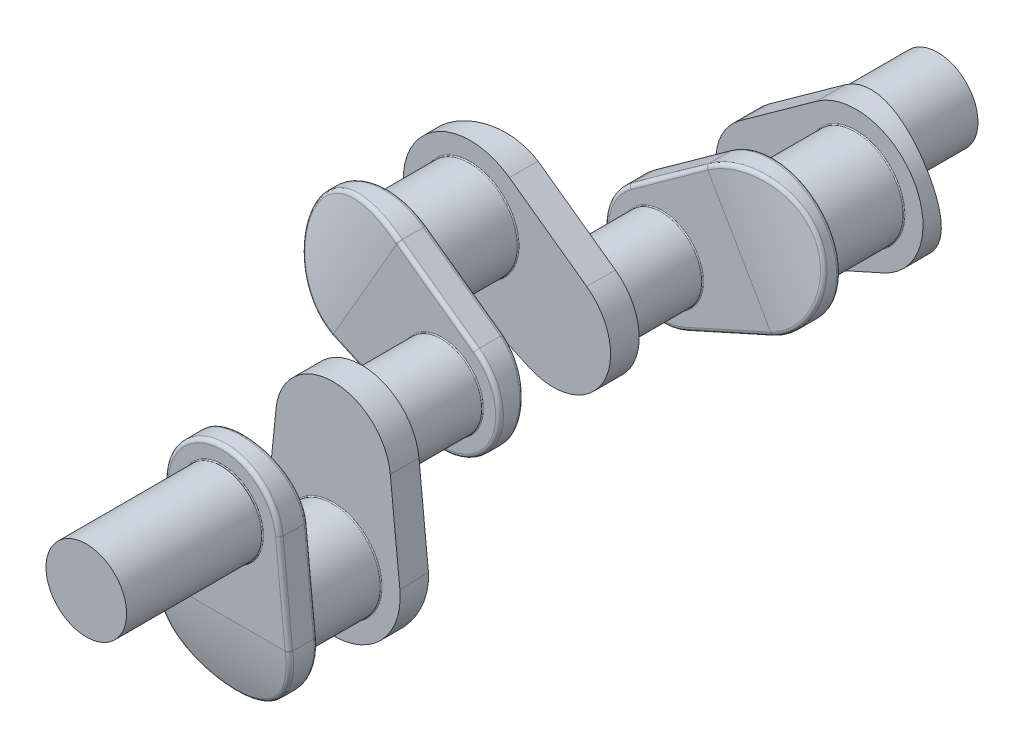
SolidWorks part; units mm, degrees
ref_plane "Front Plane" through (0, 0, 0) normal (0, 0, 1) x (1, 0, 0)
ref_plane "Top Plane" through (0, 0, 0) normal (0, 1, 0) x (1, 0, 0)
ref_plane "Right Plane" through (0, 0, 0) normal (1, 0, 0) x (0, 0, -1)
sketch "Sketch1" plane through (0, 0, 0) normal (0, 0, 1) x (1, 0, 0)
  circle A0 centre (0, 0) radius 31.75
  dimension "D1" = 63.5
extrude "Boss-Extrude1" add sketch "Sketch1" along normal blind 27.31
sketch "Sketch2" plane through (0, 0, 27.31) normal (0, 0, 1) x (1, 0, 0)
  line L0 (-37.909, 67.31) -> (-44.2272, 4.445)
  line L1 (37.909, 67.31) -> (44.2272, 4.445)
  arc A0 (-44.2272, 4.445) -> (44.2272, 4.445) centre (0, 0) ccw
  circle A2 centre (0, 0) radius 31.75 construction
  arc A3 (37.909, 67.31) -> (-37.909, 67.31) centre (0, 63.5) ccw
  dimension "D1" = 12.7
  dimension "D2" = 63.5
extrude "Boss-Extrude2" add sketch "Sketch2" along normal blind 19
sketch "Sketch3" plane through (0, 0, 46.31) normal (0, 0, 1) x (1, 0, 0)
  circle A0 centre (0, 63.5) radius 26.75
  point P3 (0, 0)
  point P4 (0, 0)
  dimension "D1" = 53.5
extrude "Boss-Extrude3" add sketch "Sketch3" along normal blind 26.67 contours A0
sketch "Sketch4" plane through (0, 0, 0) normal (1, 0, 0) x (0, 0, -1)
  line L0 (-46.31, -44.45) -> (-27.31, -44.45) construction
  line L1 (-46.31, 4.445) -> (-69.1204, 4.445)
  line L2 (-69.1204, 4.445) -> (-69.1204, -44.45)
  line L3 (-69.1204, -44.45) -> (-36.81, -44.45)
  arc A0 (-46.31, 4.445) -> (-36.81, -44.45) centre (122.5264, 11.8785) ccw
  dimension "D1" = 169
extrude "Cut-Extrude1" cut sketch "Sketch4" against normal mid plane 156.72 contours L3 A0 L1 L2
sketch "Sketch5" plane through (0, 0, 0) normal (1, 0, 0) x (0, 0, -1)
  line L0 (-27.31, 101.6) -> (-46.31, 101.6) construction
  line L1 (-27.31, 67.31) -> (-27.31, 101.6) construction
  line L2 (-32.31, 101.6) -> (-13.3458, 101.6)
  line L3 (-13.3458, 101.6) -> (-13.3458, 67.31)
  line L4 (-13.3458, 67.31) -> (-27.31, 67.31)
  arc A0 (-32.31, 101.6) -> (-27.31, 67.31) centre (-196.1603, 60.1986) cw
  dimension "D2" = 169
  dimension "D1" = 5
extrude "Cut-Extrude2" cut sketch "Sketch5" against normal mid plane 156.72
fillet "Fillet1" radius 2.54 8 edges at (41.0681, 35.8775, 46.31) (-41.0681, 35.8775, 46.31) (0, 101.6, 46.31) (-41.0681, 35.8775, 27.31) (41.0681, 35.8775, 27.31) (0, -44.45, 27.31) (0.3198, -44.4488, 36.8104) (4.6892, 101.3103, 32.2371)
fillet "Fillet2" radius 0.64 2 edges at (31.75, 0, 27.31) (26.75, 63.5, 46.31)
mirror "Mirror2" about plane through (0, 0, 0) normal (0, 0, 1) of "Boss-Extrude1", "Boss-Extrude3", "Cut-Extrude1", "Boss-Extrude2", "Fillet2"
pattern_linear "LPattern1" count 3 spacing 145.96 along (0, 0, -1) of bodies 106
ref_axis "Axis1" through (0, 63.5, 164.7872) along (0, 0, -1)
move or copy body "Body-Move/Copy1" bodies to move or copy 107 copy no rotation origin (0, 63.5, 0) rotation axis (0, 0, -1) rotation angle 120
move or copy body "Body-Move/Copy2" bodies to move or copy 108 copy no rotation origin (0, 63.5, 0) rotation axis (0, 0, 1) rotation angle 120
combine bodies "Combine4" operation type add bodies to combine 106 109 110
sketch "Sketch6" plane through (0, 0, 72.98) normal (0, 0, 1) x (1, 0, 0)
  circle A1 centre (0, 63.5) radius 26.75
  circle A2 centre (0, 63.5) radius 26.75
  dimension "D1" = 0
extrude "Boss-Extrude4" add sketch "Sketch6" along normal blind 63.5
sketch "Sketch7" plane through (0, 0, -364.9) normal (0, 0, -1) x (-1, 0, 0)
  circle A1 centre (0, 63.5) radius 26.75
  circle A2 centre (0, 63.5) radius 26.75
  dimension "D1" = 0
extrude "Boss-Extrude5" add sketch "Sketch7" along normal blind 63.5 contours A2
